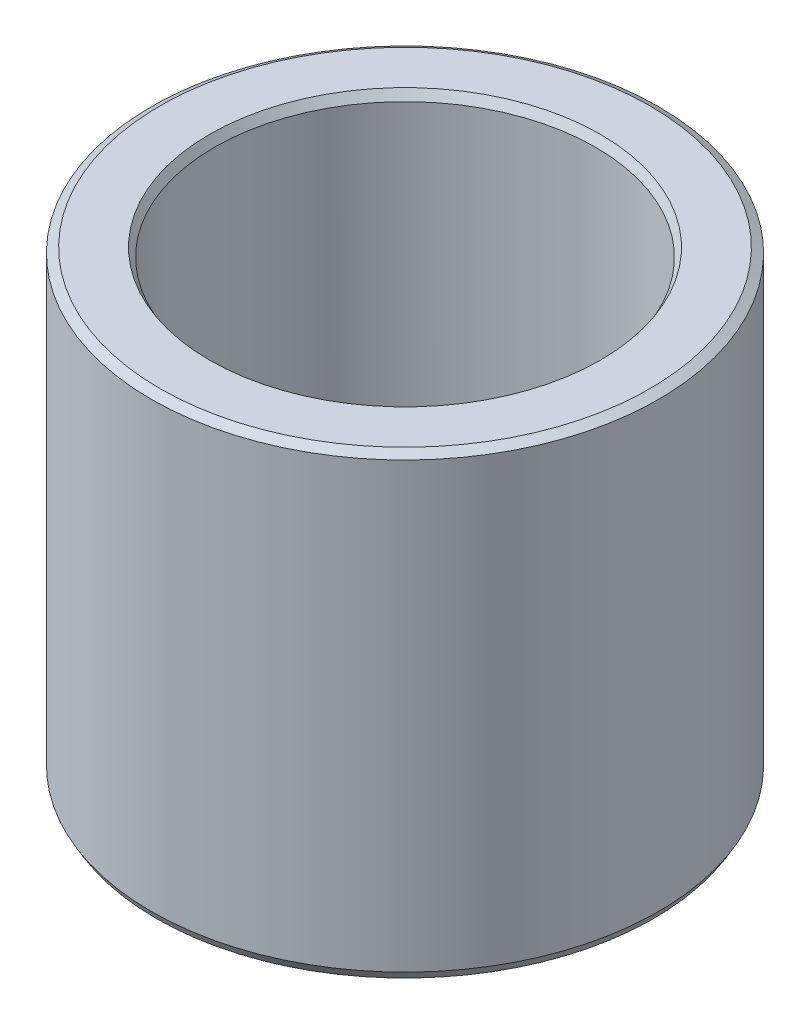
SolidWorks part; units mm, degrees
ref_plane "Front Plane" through (0, 0, 0) normal (0, 0, 1) x (1, 0, 0)
ref_plane "Top Plane" through (0, 0, 0) normal (0, 1, 0) x (1, 0, 0)
ref_plane "Right Plane" through (0, 0, 0) normal (1, 0, 0) x (0, 0, -1)
sketch "Sketch1" plane through (0, 0, 0) normal (0, 1, 0) x (1, 0, 0)
  circle A0 centre (0, 0) radius 50
  dimension "SLEEVE_OD" = 100
extrude "Boss-Extrude1" add sketch "Sketch1" along normal blind 90.1398
sketch "Sketch2" plane through (0, 0, 0) normal (0, 1, 0) x (1, 0, 0)
  circle A0 centre (0, 0) radius 37.573
  dimension "BORE_D" = 75.1459
extrude "Cut-Extrude1" cut sketch "Sketch2" along normal through all
chamfer "Chamfer1" distance 0.9824 angle 60 4 edges at (0, 90.1398, 37.573) (0, 0, 37.573) (0, 0, 50) (0, 90.1398, 50) first distance on face at (0, 90.1398, 37.573) first distance on face at (0, 0, 37.573) first distance on face at (0, 90.1398, 50)
